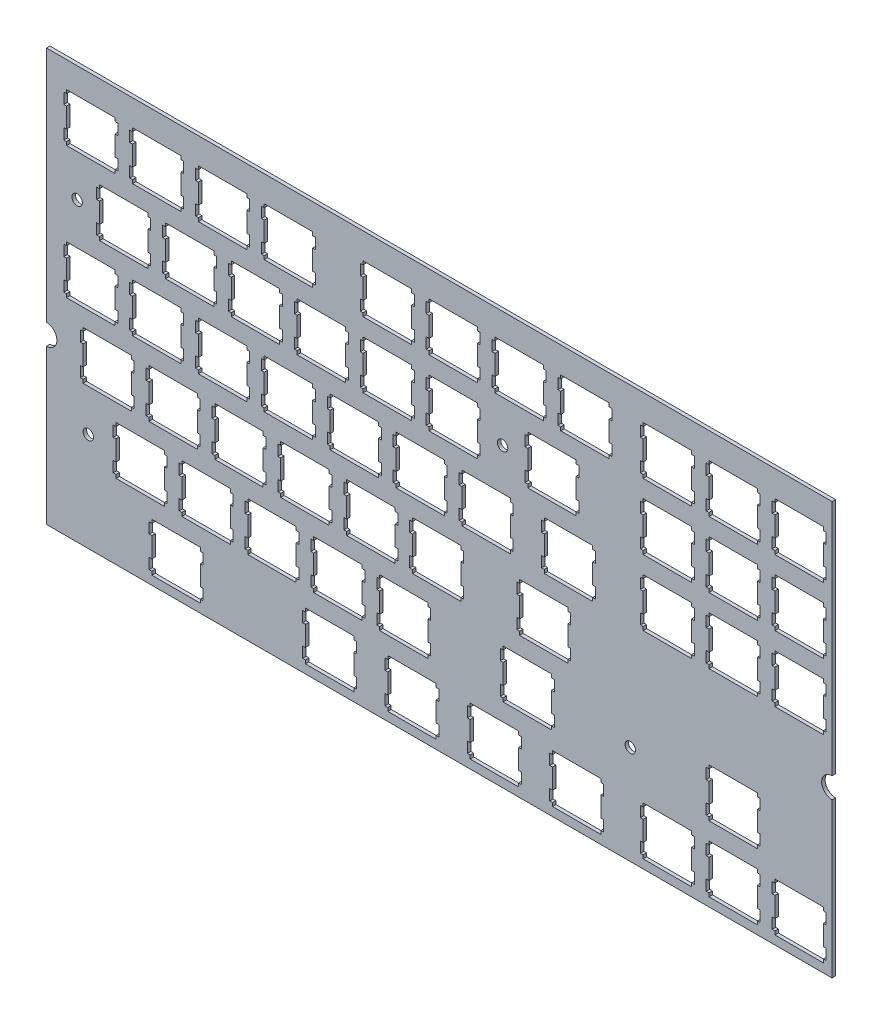
SolidWorks part; units mm, degrees
ref_plane "前视基准面" through (0, 0, 0) normal (0, 0, 1) x (1, 0, 0)
ref_plane "上视基准面" through (0, 0, 0) normal (0, 1, 0) x (1, 0, 0)
ref_plane "右视基准面" through (0, 0, 0) normal (1, 0, 0) x (0, 0, -1)
sketch "Model" plane through (0, 0, 0) normal (0, 0, 1) x (1, 0, 0)
  line L0 (406.675, 92.1112) -> (406.675, 91.1108)
  line L1 (406.675, 91.1108) -> (405.874, 91.1108)
  line L2 (405.874, 91.1108) -> (405.874, 88.0115)
  line L3 (405.874, 88.0115) -> (406.675, 88.0115)
  line L4 (406.675, 88.0115) -> (406.675, 82.21)
  line L5 (406.675, 82.21) -> (405.874, 82.21)
  line L6 (405.874, 82.21) -> (405.874, 79.1108)
  line L7 (405.874, 79.1108) -> (406.675, 79.1108)
  line L8 (406.675, 79.1108) -> (406.675, 78.1103)
  line L9 (406.675, 78.1103) -> (420.675, 78.1103)
  line L10 (420.675, 78.1103) -> (420.675, 79.1108)
  line L11 (420.675, 79.1108) -> (421.474, 79.1108)
  line L12 (421.474, 79.1108) -> (421.474, 82.21)
  line L13 (421.474, 82.21) -> (420.675, 82.21)
  line L14 (420.675, 82.21) -> (420.675, 88.0115)
  line L15 (420.675, 88.0115) -> (421.474, 88.0115)
  line L16 (421.474, 88.0115) -> (421.474, 91.1108)
  line L17 (421.474, 91.1108) -> (420.675, 91.1108)
  line L18 (420.675, 91.1108) -> (420.675, 92.1112)
  line L19 (420.675, 92.1112) -> (406.675, 92.1112)
  line L20 (387.625, 92.1112) -> (387.625, 91.1108)
  line L21 (387.625, 91.1108) -> (386.824, 91.1108)
  line L22 (386.824, 91.1108) -> (386.824, 88.0115)
  line L23 (386.824, 88.0115) -> (387.625, 88.0115)
  line L24 (387.625, 88.0115) -> (387.625, 82.21)
  line L25 (387.625, 82.21) -> (386.824, 82.21)
  line L26 (386.824, 82.21) -> (386.824, 79.1108)
  line L27 (386.824, 79.1108) -> (387.625, 79.1108)
  line L28 (387.625, 79.1108) -> (387.625, 78.1103)
  line L29 (387.625, 78.1103) -> (401.625, 78.1103)
  line L30 (401.625, 78.1103) -> (401.625, 79.1108)
  line L31 (401.625, 79.1108) -> (402.424, 79.1108)
  line L32 (402.424, 79.1108) -> (402.424, 82.21)
  line L33 (402.424, 82.21) -> (401.625, 82.21)
  line L34 (401.625, 82.21) -> (401.625, 88.0115)
  line L35 (401.625, 88.0115) -> (402.424, 88.0115)
  line L36 (402.424, 88.0115) -> (402.424, 91.1108)
  line L37 (402.424, 91.1108) -> (401.625, 91.1108)
  line L38 (401.625, 91.1108) -> (401.625, 92.1112)
  line L39 (401.625, 92.1112) -> (387.625, 92.1112)
  line L40 (368.575, 92.1112) -> (368.575, 91.1108)
  line L41 (368.575, 91.1108) -> (367.774, 91.1108)
  line L42 (367.774, 91.1108) -> (367.774, 88.0115)
  line L43 (367.774, 88.0115) -> (368.575, 88.0115)
  line L44 (368.575, 88.0115) -> (368.575, 82.21)
  line L45 (368.575, 82.21) -> (367.774, 82.21)
  line L46 (367.774, 82.21) -> (367.774, 79.1108)
  line L47 (367.774, 79.1108) -> (368.575, 79.1108)
  line L48 (368.575, 79.1108) -> (368.575, 78.1103)
  line L49 (368.575, 78.1103) -> (382.575, 78.1103)
  line L50 (382.575, 78.1103) -> (382.575, 79.1108)
  line L51 (382.575, 79.1108) -> (383.374, 79.1108)
  line L52 (383.374, 79.1108) -> (383.374, 82.21)
  line L53 (383.374, 82.21) -> (382.575, 82.21)
  line L54 (382.575, 82.21) -> (382.575, 88.0115)
  line L55 (382.575, 88.0115) -> (383.374, 88.0115)
  line L56 (383.374, 88.0115) -> (383.374, 91.1108)
  line L57 (383.374, 91.1108) -> (382.575, 91.1108)
  line L58 (382.575, 91.1108) -> (382.575, 92.1112)
  line L59 (382.575, 92.1112) -> (368.575, 92.1112)
  line L60 (342.38, 92.1112) -> (342.38, 91.1108)
  line L61 (342.38, 91.1108) -> (341.581, 91.1108)
  line L62 (341.581, 91.1108) -> (341.581, 88.0115)
  line L63 (341.581, 88.0115) -> (342.38, 88.0115)
  line L64 (342.38, 88.0115) -> (342.38, 82.21)
  line L65 (342.38, 82.21) -> (341.581, 82.21)
  line L66 (341.581, 82.21) -> (341.581, 79.1108)
  line L67 (341.581, 79.1108) -> (342.38, 79.1108)
  line L68 (342.38, 79.1108) -> (342.38, 78.1103)
  line L69 (342.38, 78.1103) -> (356.381, 78.1103)
  line L70 (356.381, 78.1103) -> (356.381, 79.1108)
  line L71 (356.381, 79.1108) -> (357.18, 79.1108)
  line L72 (357.18, 79.1108) -> (357.18, 82.21)
  line L73 (357.18, 82.21) -> (356.381, 82.21)
  line L74 (356.381, 82.21) -> (356.381, 88.0115)
  line L75 (356.381, 88.0115) -> (357.18, 88.0115)
  line L76 (357.18, 88.0115) -> (357.18, 91.1108)
  line L77 (357.18, 91.1108) -> (356.381, 91.1108)
  line L78 (356.381, 91.1108) -> (356.381, 92.1112)
  line L79 (356.381, 92.1112) -> (342.38, 92.1112)
  line L80 (318.569, 92.1112) -> (318.569, 91.1108)
  line L81 (318.569, 91.1108) -> (317.768, 91.1108)
  line L82 (317.768, 91.1108) -> (317.768, 88.0115)
  line L83 (317.768, 88.0115) -> (318.569, 88.0115)
  line L84 (318.569, 88.0115) -> (318.569, 82.21)
  line L85 (318.569, 82.21) -> (317.768, 82.21)
  line L86 (317.768, 82.21) -> (317.768, 79.1108)
  line L87 (317.768, 79.1108) -> (318.569, 79.1108)
  line L88 (318.569, 79.1108) -> (318.569, 78.1103)
  line L89 (318.569, 78.1103) -> (332.568, 78.1103)
  line L90 (332.568, 78.1103) -> (332.568, 79.1108)
  line L91 (332.568, 79.1108) -> (333.369, 79.1108)
  line L92 (333.369, 79.1108) -> (333.369, 82.21)
  line L93 (333.369, 82.21) -> (332.568, 82.21)
  line L94 (332.568, 82.21) -> (332.568, 88.0115)
  line L95 (332.568, 88.0115) -> (333.369, 88.0115)
  line L96 (333.369, 88.0115) -> (333.369, 91.1108)
  line L97 (333.369, 91.1108) -> (332.568, 91.1108)
  line L98 (332.568, 91.1108) -> (332.568, 92.1112)
  line L99 (332.568, 92.1112) -> (318.569, 92.1112)
  line L100 (294.755, 92.1112) -> (294.755, 91.1108)
  line L101 (294.755, 91.1108) -> (293.956, 91.1108)
  line L102 (293.956, 91.1108) -> (293.956, 88.0115)
  line L103 (293.956, 88.0115) -> (294.755, 88.0115)
  line L104 (294.755, 88.0115) -> (294.755, 82.21)
  line L105 (294.755, 82.21) -> (293.956, 82.21)
  line L106 (293.956, 82.21) -> (293.956, 79.1108)
  line L107 (293.956, 79.1108) -> (294.755, 79.1108)
  line L108 (294.755, 79.1108) -> (294.755, 78.1103)
  line L109 (294.755, 78.1103) -> (308.756, 78.1103)
  line L110 (308.756, 78.1103) -> (308.756, 79.1108)
  line L111 (308.756, 79.1108) -> (309.555, 79.1108)
  line L112 (309.555, 79.1108) -> (309.555, 82.21)
  line L113 (309.555, 82.21) -> (308.756, 82.21)
  line L114 (308.756, 82.21) -> (308.756, 88.0115)
  line L115 (308.756, 88.0115) -> (309.555, 88.0115)
  line L116 (309.555, 88.0115) -> (309.555, 91.1108)
  line L117 (309.555, 91.1108) -> (308.756, 91.1108)
  line L118 (308.756, 91.1108) -> (308.756, 92.1112)
  line L119 (308.756, 92.1112) -> (294.755, 92.1112)
  line L120 (270.944, 92.1112) -> (270.944, 91.1108)
  line L121 (270.944, 91.1108) -> (270.143, 91.1108)
  line L122 (270.143, 91.1108) -> (270.143, 88.0115)
  line L123 (270.143, 88.0115) -> (270.944, 88.0115)
  line L124 (270.944, 88.0115) -> (270.944, 82.21)
  line L125 (270.944, 82.21) -> (270.143, 82.21)
  line L126 (270.143, 82.21) -> (270.143, 79.1108)
  line L127 (270.143, 79.1108) -> (270.944, 79.1108)
  line L128 (270.944, 79.1108) -> (270.944, 78.1103)
  line L129 (270.944, 78.1103) -> (284.943, 78.1103)
  line L130 (284.943, 78.1103) -> (284.943, 79.1108)
  line L131 (284.943, 79.1108) -> (285.744, 79.1108)
  line L132 (285.744, 79.1108) -> (285.744, 82.21)
  line L133 (285.744, 82.21) -> (284.943, 82.21)
  line L134 (284.943, 82.21) -> (284.943, 88.0115)
  line L135 (284.943, 88.0115) -> (285.744, 88.0115)
  line L136 (285.744, 88.0115) -> (285.744, 91.1108)
  line L137 (285.744, 91.1108) -> (284.943, 91.1108)
  line L138 (284.943, 91.1108) -> (284.943, 92.1112)
  line L139 (284.943, 92.1112) -> (270.944, 92.1112)
  line L140 (387.625, 111.1597) -> (387.625, 110.1594)
  line L141 (387.625, 110.1594) -> (386.824, 110.1594)
  line L142 (386.824, 110.1594) -> (386.824, 107.0615)
  line L143 (386.824, 107.0615) -> (387.625, 107.0615)
  line L144 (387.625, 107.0615) -> (387.625, 101.26)
  line L145 (387.625, 101.26) -> (386.824, 101.26)
  line L146 (386.824, 101.26) -> (386.824, 98.1594)
  line L147 (386.824, 98.1594) -> (387.625, 98.1594)
  line L148 (387.625, 98.1594) -> (387.625, 97.1603)
  line L149 (387.625, 97.1603) -> (401.625, 97.1603)
  line L150 (401.625, 97.1603) -> (401.625, 98.1594)
  line L151 (401.625, 98.1594) -> (402.424, 98.1594)
  line L152 (402.424, 98.1594) -> (402.424, 101.26)
  line L153 (402.424, 101.26) -> (401.625, 101.26)
  line L154 (401.625, 101.26) -> (401.625, 107.0615)
  line L155 (401.625, 107.0615) -> (402.424, 107.0615)
  line L156 (402.424, 107.0615) -> (402.424, 110.1594)
  line L157 (402.424, 110.1594) -> (401.625, 110.1594)
  line L158 (401.625, 110.1594) -> (401.625, 111.1597)
  line L159 (401.625, 111.1597) -> (387.625, 111.1597)
  line L160 (292.375, 111.1597) -> (292.375, 110.1594)
  line L161 (292.375, 110.1594) -> (291.574, 110.1594)
  line L162 (291.574, 110.1594) -> (291.574, 107.0615)
  line L163 (291.574, 107.0615) -> (292.375, 107.0615)
  line L164 (292.375, 107.0615) -> (292.375, 101.26)
  line L165 (292.375, 101.26) -> (291.574, 101.26)
  line L166 (291.574, 101.26) -> (291.574, 98.1594)
  line L167 (291.574, 98.1594) -> (292.375, 98.1594)
  line L168 (292.375, 98.1594) -> (292.375, 97.1603)
  line L169 (292.375, 97.1603) -> (306.375, 97.1603)
  line L170 (306.375, 97.1603) -> (306.375, 98.1594)
  line L171 (306.375, 98.1594) -> (307.174, 98.1594)
  line L172 (307.174, 98.1594) -> (307.174, 101.26)
  line L173 (307.174, 101.26) -> (306.375, 101.26)
  line L174 (306.375, 101.26) -> (306.375, 107.0615)
  line L175 (306.375, 107.0615) -> (307.174, 107.0615)
  line L176 (307.174, 107.0615) -> (307.174, 110.1594)
  line L177 (307.174, 110.1594) -> (306.375, 110.1594)
  line L178 (306.375, 110.1594) -> (306.375, 111.1597)
  line L179 (306.375, 111.1597) -> (292.375, 111.1597)
  line L180 (273.325, 111.1597) -> (273.325, 110.1594)
  line L181 (273.325, 110.1594) -> (272.524, 110.1594)
  line L182 (272.524, 110.1594) -> (272.524, 107.0615)
  line L183 (272.524, 107.0615) -> (273.325, 107.0615)
  line L184 (273.325, 107.0615) -> (273.325, 101.26)
  line L185 (273.325, 101.26) -> (272.524, 101.26)
  line L186 (272.524, 101.26) -> (272.524, 98.1594)
  line L187 (272.524, 98.1594) -> (273.325, 98.1594)
  line L188 (273.325, 98.1594) -> (273.325, 97.1603)
  line L189 (273.325, 97.1603) -> (287.325, 97.1603)
  line L190 (287.325, 97.1603) -> (287.325, 98.1594)
  line L191 (287.325, 98.1594) -> (288.124, 98.1594)
  line L192 (288.124, 98.1594) -> (288.124, 101.26)
  line L193 (288.124, 101.26) -> (287.325, 101.26)
  line L194 (287.325, 101.26) -> (287.325, 107.0615)
  line L195 (287.325, 107.0615) -> (288.124, 107.0615)
  line L196 (288.124, 107.0615) -> (288.124, 110.1594)
  line L197 (288.124, 110.1594) -> (287.325, 110.1594)
  line L198 (287.325, 110.1594) -> (287.325, 111.1597)
  line L199 (287.325, 111.1597) -> (273.325, 111.1597)
  line L200 (254.275, 111.1597) -> (254.275, 110.1594)
  line L201 (254.275, 110.1594) -> (253.474, 110.1594)
  line L202 (253.474, 110.1594) -> (253.474, 107.0615)
  line L203 (253.474, 107.0615) -> (254.275, 107.0615)
  line L204 (254.275, 107.0615) -> (254.275, 101.26)
  line L205 (254.275, 101.26) -> (253.474, 101.26)
  line L206 (253.474, 101.26) -> (253.474, 98.1594)
  line L207 (253.474, 98.1594) -> (254.275, 98.1594)
  line L208 (254.275, 98.1594) -> (254.275, 97.1603)
  line L209 (254.275, 97.1603) -> (268.275, 97.1603)
  line L210 (268.275, 97.1603) -> (268.275, 98.1594)
  line L211 (268.275, 98.1594) -> (269.074, 98.1594)
  line L212 (269.074, 98.1594) -> (269.074, 101.26)
  line L213 (269.074, 101.26) -> (268.275, 101.26)
  line L214 (268.275, 101.26) -> (268.275, 107.0615)
  line L215 (268.275, 107.0615) -> (269.074, 107.0615)
  line L216 (269.074, 107.0615) -> (269.074, 110.1594)
  line L217 (269.074, 110.1594) -> (268.275, 110.1594)
  line L218 (268.275, 110.1594) -> (268.275, 111.1597)
  line L219 (268.275, 111.1597) -> (254.275, 111.1597)
  line L220 (235.225, 111.1597) -> (235.225, 110.1594)
  line L221 (235.225, 110.1594) -> (234.424, 110.1594)
  line L222 (234.424, 110.1594) -> (234.424, 107.0615)
  line L223 (234.424, 107.0615) -> (235.225, 107.0615)
  line L224 (235.225, 107.0615) -> (235.225, 101.26)
  line L225 (235.225, 101.26) -> (234.424, 101.26)
  line L226 (234.424, 101.26) -> (234.424, 98.1594)
  line L227 (234.424, 98.1594) -> (235.225, 98.1594)
  line L228 (235.225, 98.1594) -> (235.225, 97.1603)
  line L229 (235.225, 97.1603) -> (249.225, 97.1603)
  line L230 (249.225, 97.1603) -> (249.225, 98.1594)
  line L231 (249.225, 98.1594) -> (250.024, 98.1594)
  line L232 (250.024, 98.1594) -> (250.024, 101.26)
  line L233 (250.024, 101.26) -> (249.225, 101.26)
  line L234 (249.225, 101.26) -> (249.225, 107.0615)
  line L235 (249.225, 107.0615) -> (250.024, 107.0615)
  line L236 (250.024, 107.0615) -> (250.024, 110.1594)
  line L237 (250.024, 110.1594) -> (249.225, 110.1594)
  line L238 (249.225, 110.1594) -> (249.225, 111.1597)
  line L239 (249.225, 111.1597) -> (235.225, 111.1597)
  line L240 (216.175, 111.1597) -> (216.175, 110.1594)
  line L241 (216.175, 110.1594) -> (215.374, 110.1594)
  line L242 (215.374, 110.1594) -> (215.374, 107.0615)
  line L243 (215.374, 107.0615) -> (216.175, 107.0615)
  line L244 (216.175, 107.0615) -> (216.175, 101.26)
  line L245 (216.175, 101.26) -> (215.374, 101.26)
  line L246 (215.374, 101.26) -> (215.374, 98.1594)
  line L247 (215.374, 98.1594) -> (216.175, 98.1594)
  line L248 (216.175, 98.1594) -> (216.175, 97.1603)
  line L249 (216.175, 97.1603) -> (230.175, 97.1603)
  line L250 (230.175, 97.1603) -> (230.175, 98.1594)
  line L251 (230.175, 98.1594) -> (230.974, 98.1594)
  line L252 (230.974, 98.1594) -> (230.974, 101.26)
  line L253 (230.974, 101.26) -> (230.175, 101.26)
  line L254 (230.175, 101.26) -> (230.175, 107.0615)
  line L255 (230.175, 107.0615) -> (230.974, 107.0615)
  line L256 (230.974, 107.0615) -> (230.974, 110.1594)
  line L257 (230.974, 110.1594) -> (230.175, 110.1594)
  line L258 (230.175, 110.1594) -> (230.175, 111.1597)
  line L259 (230.175, 111.1597) -> (216.175, 111.1597)
  line L260 (332.855, 130.2098) -> (332.855, 129.2093)
  line L261 (332.855, 129.2093) -> (332.054, 129.2093)
  line L262 (332.054, 129.2093) -> (332.054, 126.1115)
  line L263 (332.054, 126.1115) -> (332.855, 126.1115)
  line L264 (332.855, 126.1115) -> (332.855, 120.3101)
  line L265 (332.855, 120.3101) -> (332.054, 120.3101)
  line L266 (332.054, 120.3101) -> (332.054, 117.2095)
  line L267 (332.054, 117.2095) -> (332.855, 117.2095)
  line L268 (332.855, 117.2095) -> (332.855, 116.2105)
  line L269 (332.855, 116.2105) -> (346.856, 116.2105)
  line L270 (346.856, 116.2105) -> (346.856, 117.2095)
  line L271 (346.856, 117.2095) -> (347.655, 117.2095)
  line L272 (347.655, 117.2095) -> (347.655, 120.3101)
  line L273 (347.655, 120.3101) -> (346.856, 120.3101)
  line L274 (346.856, 120.3101) -> (346.856, 126.1115)
  line L275 (346.856, 126.1115) -> (347.655, 126.1115)
  line L276 (347.655, 126.1115) -> (347.655, 129.2093)
  line L277 (347.655, 129.2093) -> (346.856, 129.2093)
  line L278 (346.856, 129.2093) -> (346.856, 130.2098)
  line L279 (346.856, 130.2098) -> (332.855, 130.2098)
  line L280 (301.9, 130.2098) -> (301.9, 129.2093)
  line L281 (301.9, 129.2093) -> (301.099, 129.2093)
  line L282 (301.099, 129.2093) -> (301.099, 126.1115)
  line L283 (301.099, 126.1115) -> (301.9, 126.1115)
  line L284 (301.9, 126.1115) -> (301.9, 120.3101)
  line L285 (301.9, 120.3101) -> (301.099, 120.3101)
  line L286 (301.099, 120.3101) -> (301.099, 117.2095)
  line L287 (301.099, 117.2095) -> (301.9, 117.2095)
  line L288 (301.9, 117.2095) -> (301.9, 116.2105)
  line L289 (301.9, 116.2105) -> (315.9, 116.2105)
  line L290 (315.9, 116.2105) -> (315.9, 117.2095)
  line L291 (315.9, 117.2095) -> (316.699, 117.2095)
  line L292 (316.699, 117.2095) -> (316.699, 120.3101)
  line L293 (316.699, 120.3101) -> (315.9, 120.3101)
  line L294 (315.9, 120.3101) -> (315.9, 126.1115)
  line L295 (315.9, 126.1115) -> (316.699, 126.1115)
  line L296 (316.699, 126.1115) -> (316.699, 129.2093)
  line L297 (316.699, 129.2093) -> (315.9, 129.2093)
  line L298 (315.9, 129.2093) -> (315.9, 130.2098)
  line L299 (315.9, 130.2098) -> (301.9, 130.2098)
  line L300 (282.85, 130.2098) -> (282.85, 129.2093)
  line L301 (282.85, 129.2093) -> (282.049, 129.2093)
  line L302 (282.049, 129.2093) -> (282.049, 126.1115)
  line L303 (282.049, 126.1115) -> (282.85, 126.1115)
  line L304 (282.85, 126.1115) -> (282.85, 120.3101)
  line L305 (282.85, 120.3101) -> (282.049, 120.3101)
  line L306 (282.049, 120.3101) -> (282.049, 117.2095)
  line L307 (282.049, 117.2095) -> (282.85, 117.2095)
  line L308 (282.85, 117.2095) -> (282.85, 116.2105)
  line L309 (282.85, 116.2105) -> (296.85, 116.2105)
  line L310 (296.85, 116.2105) -> (296.85, 117.2095)
  line L311 (296.85, 117.2095) -> (297.649, 117.2095)
  line L312 (297.649, 117.2095) -> (297.649, 120.3101)
  line L313 (297.649, 120.3101) -> (296.85, 120.3101)
  line L314 (296.85, 120.3101) -> (296.85, 126.1115)
  line L315 (296.85, 126.1115) -> (297.649, 126.1115)
  line L316 (297.649, 126.1115) -> (297.649, 129.2093)
  line L317 (297.649, 129.2093) -> (296.85, 129.2093)
  line L318 (296.85, 129.2093) -> (296.85, 130.2098)
  line L319 (296.85, 130.2098) -> (282.85, 130.2098)
  line L320 (263.8, 130.2098) -> (263.8, 129.2093)
  line L321 (263.8, 129.2093) -> (262.999, 129.2093)
  line L322 (262.999, 129.2093) -> (262.999, 126.1115)
  line L323 (262.999, 126.1115) -> (263.8, 126.1115)
  line L324 (263.8, 126.1115) -> (263.8, 120.3101)
  line L325 (263.8, 120.3101) -> (262.999, 120.3101)
  line L326 (262.999, 120.3101) -> (262.999, 117.2095)
  line L327 (262.999, 117.2095) -> (263.8, 117.2095)
  line L328 (263.8, 117.2095) -> (263.8, 116.2105)
  line L329 (263.8, 116.2105) -> (277.8, 116.2105)
  line L330 (277.8, 116.2105) -> (277.8, 117.2095)
  line L331 (277.8, 117.2095) -> (278.599, 117.2095)
  line L332 (278.599, 117.2095) -> (278.599, 120.3101)
  line L333 (278.599, 120.3101) -> (277.8, 120.3101)
  line L334 (277.8, 120.3101) -> (277.8, 126.1115)
  line L335 (277.8, 126.1115) -> (278.599, 126.1115)
  line L336 (278.599, 126.1115) -> (278.599, 129.2093)
  line L337 (278.599, 129.2093) -> (277.8, 129.2093)
  line L338 (277.8, 129.2093) -> (277.8, 130.2098)
  line L339 (277.8, 130.2098) -> (263.8, 130.2098)
  line L340 (244.75, 130.2098) -> (244.75, 129.2093)
  line L341 (244.75, 129.2093) -> (243.949, 129.2093)
  line L342 (243.949, 129.2093) -> (243.949, 126.1115)
  line L343 (243.949, 126.1115) -> (244.75, 126.1115)
  line L344 (244.75, 126.1115) -> (244.75, 120.3101)
  line L345 (244.75, 120.3101) -> (243.949, 120.3101)
  line L346 (243.949, 120.3101) -> (243.949, 117.2095)
  line L347 (243.949, 117.2095) -> (244.75, 117.2095)
  line L348 (244.75, 117.2095) -> (244.75, 116.2105)
  line L349 (244.75, 116.2105) -> (258.75, 116.2105)
  line L350 (258.75, 116.2105) -> (258.75, 117.2095)
  line L351 (258.75, 117.2095) -> (259.549, 117.2095)
  line L352 (259.549, 117.2095) -> (259.549, 120.3101)
  line L353 (259.549, 120.3101) -> (258.75, 120.3101)
  line L354 (258.75, 120.3101) -> (258.75, 126.1115)
  line L355 (258.75, 126.1115) -> (259.549, 126.1115)
  line L356 (259.549, 126.1115) -> (259.549, 129.2093)
  line L357 (259.549, 129.2093) -> (258.75, 129.2093)
  line L358 (258.75, 129.2093) -> (258.75, 130.2098)
  line L359 (258.75, 130.2098) -> (244.75, 130.2098)
  line L360 (225.7, 130.2098) -> (225.7, 129.2093)
  line L361 (225.7, 129.2093) -> (224.899, 129.2093)
  line L362 (224.899, 129.2093) -> (224.899, 126.1115)
  line L363 (224.899, 126.1115) -> (225.7, 126.1115)
  line L364 (225.7, 126.1115) -> (225.7, 120.3101)
  line L365 (225.7, 120.3101) -> (224.899, 120.3101)
  line L366 (224.899, 120.3101) -> (224.899, 117.2095)
  line L367 (224.899, 117.2095) -> (225.7, 117.2095)
  line L368 (225.7, 117.2095) -> (225.7, 116.2105)
  line L369 (225.7, 116.2105) -> (239.7, 116.2105)
  line L370 (239.7, 116.2105) -> (239.7, 117.2095)
  line L371 (239.7, 117.2095) -> (240.499, 117.2095)
  line L372 (240.499, 117.2095) -> (240.499, 120.3101)
  line L373 (240.499, 120.3101) -> (239.7, 120.3101)
  line L374 (239.7, 120.3101) -> (239.7, 126.1115)
  line L375 (239.7, 126.1115) -> (240.499, 126.1115)
  line L376 (240.499, 126.1115) -> (240.499, 129.2093)
  line L377 (240.499, 129.2093) -> (239.7, 129.2093)
  line L378 (239.7, 129.2093) -> (239.7, 130.2098)
  line L379 (239.7, 130.2098) -> (225.7, 130.2098)
  line L380 (206.65, 130.2098) -> (206.65, 129.2093)
  line L381 (206.65, 129.2093) -> (205.849, 129.2093)
  line L382 (205.849, 129.2093) -> (205.849, 126.1115)
  line L383 (205.849, 126.1115) -> (206.65, 126.1115)
  line L384 (206.65, 126.1115) -> (206.65, 120.3101)
  line L385 (206.65, 120.3101) -> (205.849, 120.3101)
  line L386 (205.849, 120.3101) -> (205.849, 117.2095)
  line L387 (205.849, 117.2095) -> (206.65, 117.2095)
  line L388 (206.65, 117.2095) -> (206.65, 116.2105)
  line L389 (206.65, 116.2105) -> (220.65, 116.2105)
  line L390 (220.65, 116.2105) -> (220.65, 117.2095)
  line L391 (220.65, 117.2095) -> (221.449, 117.2095)
  line L392 (221.449, 117.2095) -> (221.449, 120.3101)
  line L393 (221.449, 120.3101) -> (220.65, 120.3101)
  line L394 (220.65, 120.3101) -> (220.65, 126.1115)
  line L395 (220.65, 126.1115) -> (221.449, 126.1115)
  line L396 (221.449, 126.1115) -> (221.449, 129.2093)
  line L397 (221.449, 129.2093) -> (220.65, 129.2093)
  line L398 (220.65, 129.2093) -> (220.65, 130.2098)
  line L399 (220.65, 130.2098) -> (206.65, 130.2098)
  line L400 (406.675, 149.2598) -> (406.675, 148.2593)
  line L401 (406.675, 148.2593) -> (405.874, 148.2593)
  line L402 (405.874, 148.2593) -> (405.874, 145.1601)
  line L403 (405.874, 145.1601) -> (406.675, 145.1601)
  line L404 (406.675, 145.1601) -> (406.675, 139.3601)
  line L405 (406.675, 139.3601) -> (405.874, 139.3601)
  line L406 (405.874, 139.3601) -> (405.874, 136.2595)
  line L407 (405.874, 136.2595) -> (406.675, 136.2595)
  line L408 (406.675, 136.2595) -> (406.675, 135.2605)
  line L409 (406.675, 135.2605) -> (420.675, 135.2605)
  line L410 (420.675, 135.2605) -> (420.675, 136.2595)
  line L411 (420.675, 136.2595) -> (421.474, 136.2595)
  line L412 (421.474, 136.2595) -> (421.474, 139.3601)
  line L413 (421.474, 139.3601) -> (420.675, 139.3601)
  line L414 (420.675, 139.3601) -> (420.675, 145.1601)
  line L415 (420.675, 145.1601) -> (421.474, 145.1601)
  line L416 (421.474, 145.1601) -> (421.474, 148.2593)
  line L417 (421.474, 148.2593) -> (420.675, 148.2593)
  line L418 (420.675, 148.2593) -> (420.675, 149.2598)
  line L419 (420.675, 149.2598) -> (406.675, 149.2598)
  line L420 (387.625, 149.2598) -> (387.625, 148.2593)
  line L421 (387.625, 148.2593) -> (386.824, 148.2593)
  line L422 (386.824, 148.2593) -> (386.824, 145.1601)
  line L423 (386.824, 145.1601) -> (387.625, 145.1601)
  line L424 (387.625, 145.1601) -> (387.625, 139.3601)
  line L425 (387.625, 139.3601) -> (386.824, 139.3601)
  line L426 (386.824, 139.3601) -> (386.824, 136.2595)
  line L427 (386.824, 136.2595) -> (387.625, 136.2595)
  line L428 (387.625, 136.2595) -> (387.625, 135.2605)
  line L429 (387.625, 135.2605) -> (401.625, 135.2605)
  line L430 (401.625, 135.2605) -> (401.625, 136.2595)
  line L431 (401.625, 136.2595) -> (402.424, 136.2595)
  line L432 (402.424, 136.2595) -> (402.424, 139.3601)
  line L433 (402.424, 139.3601) -> (401.625, 139.3601)
  line L434 (401.625, 139.3601) -> (401.625, 145.1601)
  line L435 (401.625, 145.1601) -> (402.424, 145.1601)
  line L436 (402.424, 145.1601) -> (402.424, 148.2593)
  line L437 (402.424, 148.2593) -> (401.625, 148.2593)
  line L438 (401.625, 148.2593) -> (401.625, 149.2598)
  line L439 (401.625, 149.2598) -> (387.625, 149.2598)
  line L440 (368.575, 149.2598) -> (368.575, 148.2593)
  line L441 (368.575, 148.2593) -> (367.774, 148.2593)
  line L442 (367.774, 148.2593) -> (367.774, 145.1601)
  line L443 (367.774, 145.1601) -> (368.575, 145.1601)
  line L444 (368.575, 145.1601) -> (368.575, 139.3601)
  line L445 (368.575, 139.3601) -> (367.774, 139.3601)
  line L446 (367.774, 139.3601) -> (367.774, 136.2595)
  line L447 (367.774, 136.2595) -> (368.575, 136.2595)
  line L448 (368.575, 136.2595) -> (368.575, 135.2605)
  line L449 (368.575, 135.2605) -> (382.575, 135.2605)
  line L450 (382.575, 135.2605) -> (382.575, 136.2595)
  line L451 (382.575, 136.2595) -> (383.374, 136.2595)
  line L452 (383.374, 136.2595) -> (383.374, 139.3601)
  line L453 (383.374, 139.3601) -> (382.575, 139.3601)
  line L454 (382.575, 139.3601) -> (382.575, 145.1601)
  line L455 (382.575, 145.1601) -> (383.374, 145.1601)
  line L456 (383.374, 145.1601) -> (383.374, 148.2593)
  line L457 (383.374, 148.2593) -> (382.575, 148.2593)
  line L458 (382.575, 148.2593) -> (382.575, 149.2598)
  line L459 (382.575, 149.2598) -> (368.575, 149.2598)
  line L460 (340, 149.2598) -> (340, 148.2593)
  line L461 (340, 148.2593) -> (339.199, 148.2593)
  line L462 (339.199, 148.2593) -> (339.199, 145.1601)
  line L463 (339.199, 145.1601) -> (340, 145.1601)
  line L464 (340, 145.1601) -> (340, 139.3601)
  line L465 (340, 139.3601) -> (339.199, 139.3601)
  line L466 (339.199, 139.3601) -> (339.199, 136.2595)
  line L467 (339.199, 136.2595) -> (340, 136.2595)
  line L468 (340, 136.2595) -> (340, 135.2605)
  line L469 (340, 135.2605) -> (354, 135.2605)
  line L470 (354, 135.2605) -> (354, 136.2595)
  line L471 (354, 136.2595) -> (354.799, 136.2595)
  line L472 (354.799, 136.2595) -> (354.799, 139.3601)
  line L473 (354.799, 139.3601) -> (354, 139.3601)
  line L474 (354, 139.3601) -> (354, 145.1601)
  line L475 (354, 145.1601) -> (354.799, 145.1601)
  line L476 (354.799, 145.1601) -> (354.799, 148.2593)
  line L477 (354.799, 148.2593) -> (354, 148.2593)
  line L478 (354, 148.2593) -> (354, 149.2598)
  line L479 (354, 149.2598) -> (340, 149.2598)
  line L480 (316.188, 149.2598) -> (316.188, 148.2593)
  line L481 (316.188, 148.2593) -> (315.387, 148.2593)
  line L482 (315.387, 148.2593) -> (315.387, 145.1601)
  line L483 (315.387, 145.1601) -> (316.188, 145.1601)
  line L484 (316.188, 145.1601) -> (316.188, 139.3601)
  line L485 (316.188, 139.3601) -> (315.387, 139.3601)
  line L486 (315.387, 139.3601) -> (315.387, 136.2595)
  line L487 (315.387, 136.2595) -> (316.188, 136.2595)
  line L488 (316.188, 136.2595) -> (316.188, 135.2605)
  line L489 (316.188, 135.2605) -> (330.187, 135.2605)
  line L490 (330.187, 135.2605) -> (330.187, 136.2595)
  line L491 (330.187, 136.2595) -> (330.988, 136.2595)
  line L492 (330.988, 136.2595) -> (330.988, 139.3601)
  line L493 (330.988, 139.3601) -> (330.187, 139.3601)
  line L494 (330.187, 139.3601) -> (330.187, 145.1601)
  line L495 (330.187, 145.1601) -> (330.988, 145.1601)
  line L496 (330.988, 145.1601) -> (330.988, 148.2593)
  line L497 (330.988, 148.2593) -> (330.187, 148.2593)
  line L498 (330.187, 148.2593) -> (330.187, 149.2598)
  line L499 (330.187, 149.2598) -> (316.188, 149.2598)
  line L500 (297.138, 149.2598) -> (297.138, 148.2593)
  line L501 (297.138, 148.2593) -> (296.337, 148.2593)
  line L502 (296.337, 148.2593) -> (296.337, 145.1601)
  line L503 (296.337, 145.1601) -> (297.138, 145.1601)
  line L504 (297.138, 145.1601) -> (297.138, 139.3601)
  line L505 (297.138, 139.3601) -> (296.337, 139.3601)
  line L506 (296.337, 139.3601) -> (296.337, 136.2595)
  line L507 (296.337, 136.2595) -> (297.138, 136.2595)
  line L508 (297.138, 136.2595) -> (297.138, 135.2605)
  line L509 (297.138, 135.2605) -> (311.137, 135.2605)
  line L510 (311.137, 135.2605) -> (311.137, 136.2595)
  line L511 (311.137, 136.2595) -> (311.938, 136.2595)
  line L512 (311.938, 136.2595) -> (311.938, 139.3601)
  line L513 (311.938, 139.3601) -> (311.137, 139.3601)
  line L514 (311.137, 139.3601) -> (311.137, 145.1601)
  line L515 (311.137, 145.1601) -> (311.938, 145.1601)
  line L516 (311.938, 145.1601) -> (311.938, 148.2593)
  line L517 (311.938, 148.2593) -> (311.137, 148.2593)
  line L518 (311.137, 148.2593) -> (311.137, 149.2598)
  line L519 (311.137, 149.2598) -> (297.138, 149.2598)
  line L520 (278.088, 149.2598) -> (278.088, 148.2593)
  line L521 (278.088, 148.2593) -> (277.287, 148.2593)
  line L522 (277.287, 148.2593) -> (277.287, 145.1601)
  line L523 (277.287, 145.1601) -> (278.088, 145.1601)
  line L524 (278.088, 145.1601) -> (278.088, 139.3601)
  line L525 (278.088, 139.3601) -> (277.287, 139.3601)
  line L526 (277.287, 139.3601) -> (277.287, 136.2595)
  line L527 (277.287, 136.2595) -> (278.088, 136.2595)
  line L528 (278.088, 136.2595) -> (278.088, 135.2605)
  line L529 (278.088, 135.2605) -> (292.087, 135.2605)
  line L530 (292.087, 135.2605) -> (292.087, 136.2595)
  line L531 (292.087, 136.2595) -> (292.888, 136.2595)
  line L532 (292.888, 136.2595) -> (292.888, 139.3601)
  line L533 (292.888, 139.3601) -> (292.087, 139.3601)
  line L534 (292.087, 139.3601) -> (292.087, 145.1601)
  line L535 (292.087, 145.1601) -> (292.888, 145.1601)
  line L536 (292.888, 145.1601) -> (292.888, 148.2593)
  line L537 (292.888, 148.2593) -> (292.087, 148.2593)
  line L538 (292.087, 148.2593) -> (292.087, 149.2598)
  line L539 (292.087, 149.2598) -> (278.088, 149.2598)
  line L540 (259.038, 149.2598) -> (259.038, 148.2593)
  line L541 (259.038, 148.2593) -> (258.237, 148.2593)
  line L542 (258.237, 148.2593) -> (258.237, 145.1601)
  line L543 (258.237, 145.1601) -> (259.038, 145.1601)
  line L544 (259.038, 145.1601) -> (259.038, 139.3601)
  line L545 (259.038, 139.3601) -> (258.237, 139.3601)
  line L546 (258.237, 139.3601) -> (258.237, 136.2595)
  line L547 (258.237, 136.2595) -> (259.038, 136.2595)
  line L548 (259.038, 136.2595) -> (259.038, 135.2605)
  line L549 (259.038, 135.2605) -> (273.037, 135.2605)
  line L550 (273.037, 135.2605) -> (273.037, 136.2595)
  line L551 (273.037, 136.2595) -> (273.838, 136.2595)
  line L552 (273.838, 136.2595) -> (273.838, 139.3601)
  line L553 (273.838, 139.3601) -> (273.037, 139.3601)
  line L554 (273.037, 139.3601) -> (273.037, 145.1601)
  line L555 (273.037, 145.1601) -> (273.838, 145.1601)
  line L556 (273.838, 145.1601) -> (273.838, 148.2593)
  line L557 (273.838, 148.2593) -> (273.037, 148.2593)
  line L558 (273.037, 148.2593) -> (273.037, 149.2598)
  line L559 (273.037, 149.2598) -> (259.038, 149.2598)
  line L560 (239.988, 149.2598) -> (239.988, 148.2593)
  line L561 (239.988, 148.2593) -> (239.187, 148.2593)
  line L562 (239.187, 148.2593) -> (239.187, 145.1601)
  line L563 (239.187, 145.1601) -> (239.988, 145.1601)
  line L564 (239.988, 145.1601) -> (239.988, 139.3601)
  line L565 (239.988, 139.3601) -> (239.187, 139.3601)
  line L566 (239.187, 139.3601) -> (239.187, 136.2595)
  line L567 (239.187, 136.2595) -> (239.988, 136.2595)
  line L568 (239.988, 136.2595) -> (239.988, 135.2605)
  line L569 (239.988, 135.2605) -> (253.987, 135.2605)
  line L570 (253.987, 135.2605) -> (253.987, 136.2595)
  line L571 (253.987, 136.2595) -> (254.788, 136.2595)
  line L572 (254.788, 136.2595) -> (254.788, 139.3601)
  line L573 (254.788, 139.3601) -> (253.987, 139.3601)
  line L574 (253.987, 139.3601) -> (253.987, 145.1601)
  line L575 (253.987, 145.1601) -> (254.788, 145.1601)
  line L576 (254.788, 145.1601) -> (254.788, 148.2593)
  line L577 (254.788, 148.2593) -> (253.987, 148.2593)
  line L578 (253.987, 148.2593) -> (253.987, 149.2598)
  line L579 (253.987, 149.2598) -> (239.988, 149.2598)
  line L580 (220.938, 149.2598) -> (220.938, 148.2593)
  line L581 (220.938, 148.2593) -> (220.137, 148.2593)
  line L582 (220.137, 148.2593) -> (220.137, 145.1601)
  line L583 (220.137, 145.1601) -> (220.938, 145.1601)
  line L584 (220.938, 145.1601) -> (220.938, 139.3601)
  line L585 (220.938, 139.3601) -> (220.137, 139.3601)
  line L586 (220.137, 139.3601) -> (220.137, 136.2595)
  line L587 (220.137, 136.2595) -> (220.938, 136.2595)
  line L588 (220.938, 136.2595) -> (220.938, 135.2605)
  line L589 (220.938, 135.2605) -> (234.937, 135.2605)
  line L590 (234.937, 135.2605) -> (234.937, 136.2595)
  line L591 (234.937, 136.2595) -> (235.738, 136.2595)
  line L592 (235.738, 136.2595) -> (235.738, 139.3601)
  line L593 (235.738, 139.3601) -> (234.937, 139.3601)
  line L594 (234.937, 139.3601) -> (234.937, 145.1601)
  line L595 (234.937, 145.1601) -> (235.738, 145.1601)
  line L596 (235.738, 145.1601) -> (235.738, 148.2593)
  line L597 (235.738, 148.2593) -> (234.937, 148.2593)
  line L598 (234.937, 148.2593) -> (234.937, 149.2598)
  line L599 (234.937, 149.2598) -> (220.938, 149.2598)
  line L600 (201.888, 135.2605) -> (215.887, 135.2605)
  line L601 (215.887, 135.2605) -> (215.887, 136.2595)
  line L602 (215.887, 136.2595) -> (216.688, 136.2595)
  line L603 (216.688, 136.2595) -> (216.688, 139.3601)
  line L604 (216.688, 139.3601) -> (215.887, 139.3601)
  line L605 (215.887, 139.3601) -> (215.887, 145.1601)
  line L606 (215.887, 145.1601) -> (216.688, 145.1601)
  line L607 (216.688, 145.1601) -> (216.688, 148.2593)
  line L608 (216.688, 148.2593) -> (215.887, 148.2593)
  line L609 (215.887, 148.2593) -> (215.887, 149.2598)
  line L610 (215.887, 149.2598) -> (201.888, 149.2598)
  line L611 (406.675, 168.3098) -> (406.675, 167.3093)
  line L612 (406.675, 167.3093) -> (405.874, 167.3093)
  line L613 (405.874, 167.3093) -> (405.874, 164.2101)
  line L614 (405.874, 164.2101) -> (406.675, 164.2101)
  line L615 (406.675, 164.2101) -> (406.675, 158.4101)
  line L616 (406.675, 158.4101) -> (405.874, 158.4101)
  line L617 (405.874, 158.4101) -> (405.874, 155.3095)
  line L618 (405.874, 155.3095) -> (406.675, 155.3095)
  line L619 (406.675, 155.3095) -> (406.675, 154.3105)
  line L620 (406.675, 154.3105) -> (420.675, 154.3105)
  line L621 (420.675, 154.3105) -> (420.675, 155.3095)
  line L622 (420.675, 155.3095) -> (421.474, 155.3095)
  line L623 (421.474, 155.3095) -> (421.474, 158.4101)
  line L624 (421.474, 158.4101) -> (420.675, 158.4101)
  line L625 (420.675, 158.4101) -> (420.675, 164.2101)
  line L626 (420.675, 164.2101) -> (421.474, 164.2101)
  line L627 (421.474, 164.2101) -> (421.474, 167.3093)
  line L628 (421.474, 167.3093) -> (420.675, 167.3093)
  line L629 (420.675, 167.3093) -> (420.675, 168.3098)
  line L630 (420.675, 168.3098) -> (406.675, 168.3098)
  line L631 (387.625, 168.3098) -> (387.625, 167.3093)
  line L632 (387.625, 167.3093) -> (386.824, 167.3093)
  line L633 (386.824, 167.3093) -> (386.824, 164.2101)
  line L634 (386.824, 164.2101) -> (387.625, 164.2101)
  line L635 (387.625, 164.2101) -> (387.625, 158.4101)
  line L636 (387.625, 158.4101) -> (386.824, 158.4101)
  line L637 (386.824, 158.4101) -> (386.824, 155.3095)
  line L638 (386.824, 155.3095) -> (387.625, 155.3095)
  line L639 (387.625, 155.3095) -> (387.625, 154.3105)
  line L640 (387.625, 154.3105) -> (401.625, 154.3105)
  line L641 (401.625, 154.3105) -> (401.625, 155.3095)
  line L642 (401.625, 155.3095) -> (402.424, 155.3095)
  line L643 (402.424, 155.3095) -> (402.424, 158.4101)
  line L644 (402.424, 158.4101) -> (401.625, 158.4101)
  line L645 (401.625, 158.4101) -> (401.625, 164.2101)
  line L646 (401.625, 164.2101) -> (402.424, 164.2101)
  line L647 (402.424, 164.2101) -> (402.424, 167.3093)
  line L648 (402.424, 167.3093) -> (401.625, 167.3093)
  line L649 (401.625, 167.3093) -> (401.625, 168.3098)
  line L650 (401.625, 168.3098) -> (387.625, 168.3098)
  line L651 (368.575, 168.3098) -> (368.575, 167.3093)
  line L652 (368.575, 167.3093) -> (367.774, 167.3093)
  line L653 (367.774, 167.3093) -> (367.774, 164.2101)
  line L654 (367.774, 164.2101) -> (368.575, 164.2101)
  line L655 (368.575, 164.2101) -> (368.575, 158.4101)
  line L656 (368.575, 158.4101) -> (367.774, 158.4101)
  line L657 (367.774, 158.4101) -> (367.774, 155.3095)
  line L658 (367.774, 155.3095) -> (368.575, 155.3095)
  line L659 (368.575, 155.3095) -> (368.575, 154.3105)
  line L660 (368.575, 154.3105) -> (382.575, 154.3105)
  line L661 (382.575, 154.3105) -> (382.575, 155.3095)
  line L662 (382.575, 155.3095) -> (383.374, 155.3095)
  line L663 (383.374, 155.3095) -> (383.374, 158.4101)
  line L664 (383.374, 158.4101) -> (382.575, 158.4101)
  line L665 (382.575, 158.4101) -> (382.575, 164.2101)
  line L666 (382.575, 164.2101) -> (383.374, 164.2101)
  line L667 (383.374, 164.2101) -> (383.374, 167.3093)
  line L668 (383.374, 167.3093) -> (382.575, 167.3093)
  line L669 (382.575, 167.3093) -> (382.575, 168.3098)
  line L670 (382.575, 168.3098) -> (368.575, 168.3098)
  line L671 (306.663, 168.3098) -> (306.663, 167.3093)
  line L672 (306.663, 167.3093) -> (305.862, 167.3093)
  line L673 (305.862, 167.3093) -> (305.862, 164.2101)
  line L674 (305.862, 164.2101) -> (306.663, 164.2101)
  line L675 (306.663, 164.2101) -> (306.663, 158.4101)
  line L676 (306.663, 158.4101) -> (305.862, 158.4101)
  line L677 (305.862, 158.4101) -> (305.862, 155.3095)
  line L678 (305.862, 155.3095) -> (306.663, 155.3095)
  line L679 (306.663, 155.3095) -> (306.663, 154.3105)
  line L680 (306.663, 154.3105) -> (320.662, 154.3105)
  line L681 (320.662, 154.3105) -> (320.662, 155.3095)
  line L682 (320.662, 155.3095) -> (321.463, 155.3095)
  line L683 (321.463, 155.3095) -> (321.463, 158.4101)
  line L684 (321.463, 158.4101) -> (320.662, 158.4101)
  line L685 (320.662, 158.4101) -> (320.662, 164.2101)
  line L686 (320.662, 164.2101) -> (321.463, 164.2101)
  line L687 (321.463, 164.2101) -> (321.463, 167.3093)
  line L688 (321.463, 167.3093) -> (320.662, 167.3093)
  line L689 (320.662, 167.3093) -> (320.662, 168.3098)
  line L690 (320.662, 168.3098) -> (306.663, 168.3098)
  line L691 (287.613, 168.3098) -> (287.613, 167.3093)
  line L692 (287.613, 167.3093) -> (286.812, 167.3093)
  line L693 (286.812, 167.3093) -> (286.812, 164.2101)
  line L694 (286.812, 164.2101) -> (287.613, 164.2101)
  line L695 (287.613, 164.2101) -> (287.613, 158.4101)
  line L696 (287.613, 158.4101) -> (286.812, 158.4101)
  line L697 (286.812, 158.4101) -> (286.812, 155.3095)
  line L698 (286.812, 155.3095) -> (287.613, 155.3095)
  line L699 (287.613, 155.3095) -> (287.613, 154.3105)
  line L700 (287.613, 154.3105) -> (301.612, 154.3105)
  line L701 (301.612, 154.3105) -> (301.612, 155.3095)
  line L702 (301.612, 155.3095) -> (302.413, 155.3095)
  line L703 (302.413, 155.3095) -> (302.413, 158.4101)
  line L704 (302.413, 158.4101) -> (301.612, 158.4101)
  line L705 (301.612, 158.4101) -> (301.612, 164.2101)
  line L706 (301.612, 164.2101) -> (302.413, 164.2101)
  line L707 (302.413, 164.2101) -> (302.413, 167.3093)
  line L708 (302.413, 167.3093) -> (301.612, 167.3093)
  line L709 (301.612, 167.3093) -> (301.612, 168.3098)
  line L710 (301.612, 168.3098) -> (287.613, 168.3098)
  line L711 (268.563, 168.3098) -> (268.563, 167.3093)
  line L712 (268.563, 167.3093) -> (267.762, 167.3093)
  line L713 (267.762, 167.3093) -> (267.762, 164.2101)
  line L714 (267.762, 164.2101) -> (268.563, 164.2101)
  line L715 (268.563, 164.2101) -> (268.563, 158.4101)
  line L716 (268.563, 158.4101) -> (267.762, 158.4101)
  line L717 (267.762, 158.4101) -> (267.762, 155.3095)
  line L718 (267.762, 155.3095) -> (268.563, 155.3095)
  line L719 (268.563, 155.3095) -> (268.563, 154.3105)
  line L720 (268.563, 154.3105) -> (282.562, 154.3105)
  line L721 (282.562, 154.3105) -> (282.562, 155.3095)
  line L722 (282.562, 155.3095) -> (283.363, 155.3095)
  line L723 (283.363, 155.3095) -> (283.363, 158.4101)
  line L724 (283.363, 158.4101) -> (282.562, 158.4101)
  line L725 (282.562, 158.4101) -> (282.562, 164.2101)
  line L726 (282.562, 164.2101) -> (283.363, 164.2101)
  line L727 (283.363, 164.2101) -> (283.363, 167.3093)
  line L728 (283.363, 167.3093) -> (282.562, 167.3093)
  line L729 (282.562, 167.3093) -> (282.562, 168.3098)
  line L730 (282.562, 168.3098) -> (268.563, 168.3098)
  line L731 (249.513, 168.3098) -> (249.513, 167.3093)
  line L732 (249.513, 167.3093) -> (248.712, 167.3093)
  line L733 (248.712, 167.3093) -> (248.712, 164.2101)
  line L734 (248.712, 164.2101) -> (249.513, 164.2101)
  line L735 (249.513, 164.2101) -> (249.513, 158.4101)
  line L736 (249.513, 158.4101) -> (248.712, 158.4101)
  line L737 (248.712, 158.4101) -> (248.712, 155.3095)
  line L738 (248.712, 155.3095) -> (249.513, 155.3095)
  line L739 (249.513, 155.3095) -> (249.513, 154.3105)
  line L740 (249.513, 154.3105) -> (263.512, 154.3105)
  line L741 (263.512, 154.3105) -> (263.512, 155.3095)
  line L742 (263.512, 155.3095) -> (264.313, 155.3095)
  line L743 (264.313, 155.3095) -> (264.313, 158.4101)
  line L744 (264.313, 158.4101) -> (263.512, 158.4101)
  line L745 (263.512, 158.4101) -> (263.512, 164.2101)
  line L746 (263.512, 164.2101) -> (264.313, 164.2101)
  line L747 (264.313, 164.2101) -> (264.313, 167.3093)
  line L748 (264.313, 167.3093) -> (263.512, 167.3093)
  line L749 (263.512, 167.3093) -> (263.512, 168.3098)
  line L750 (263.512, 168.3098) -> (249.513, 168.3098)
  line L751 (230.463, 168.3098) -> (230.463, 167.3093)
  line L752 (230.463, 167.3093) -> (229.662, 167.3093)
  line L753 (229.662, 167.3093) -> (229.662, 164.2101)
  line L754 (229.662, 164.2101) -> (230.463, 164.2101)
  line L755 (230.463, 164.2101) -> (230.463, 158.4101)
  line L756 (230.463, 158.4101) -> (229.662, 158.4101)
  line L757 (229.662, 158.4101) -> (229.662, 155.3095)
  line L758 (229.662, 155.3095) -> (230.463, 155.3095)
  line L759 (230.463, 155.3095) -> (230.463, 154.3105)
  line L760 (230.463, 154.3105) -> (244.462, 154.3105)
  line L761 (244.462, 154.3105) -> (244.462, 155.3095)
  line L762 (244.462, 155.3095) -> (245.263, 155.3095)
  line L763 (245.263, 155.3095) -> (245.263, 158.4101)
  line L764 (245.263, 158.4101) -> (244.462, 158.4101)
  line L765 (244.462, 158.4101) -> (244.462, 164.2101)
  line L766 (244.462, 164.2101) -> (245.263, 164.2101)
  line L767 (245.263, 164.2101) -> (245.263, 167.3093)
  line L768 (245.263, 167.3093) -> (244.462, 167.3093)
  line L769 (244.462, 167.3093) -> (244.462, 168.3098)
  line L770 (244.462, 168.3098) -> (230.463, 168.3098)
  line L771 (211.413, 168.3098) -> (211.413, 167.3093)
  line L772 (211.413, 167.3093) -> (210.612, 167.3093)
  line L773 (210.612, 167.3093) -> (210.612, 164.2101)
  line L774 (210.612, 164.2101) -> (211.413, 164.2101)
  line L775 (211.413, 164.2101) -> (211.413, 158.4101)
  line L776 (211.413, 158.4101) -> (210.612, 158.4101)
  line L777 (210.612, 158.4101) -> (210.612, 155.3095)
  line L778 (210.612, 155.3095) -> (211.413, 155.3095)
  line L779 (211.413, 155.3095) -> (211.413, 154.3105)
  line L780 (211.413, 154.3105) -> (225.412, 154.3105)
  line L781 (225.412, 154.3105) -> (225.412, 155.3095)
  line L782 (225.412, 155.3095) -> (226.213, 155.3095)
  line L783 (226.213, 155.3095) -> (226.213, 158.4101)
  line L784 (226.213, 158.4101) -> (225.412, 158.4101)
  line L785 (225.412, 158.4101) -> (225.412, 164.2101)
  line L786 (225.412, 164.2101) -> (226.213, 164.2101)
  line L787 (226.213, 164.2101) -> (226.213, 167.3093)
  line L788 (226.213, 167.3093) -> (225.412, 167.3093)
  line L789 (225.412, 167.3093) -> (225.412, 168.3098)
  line L790 (225.412, 168.3098) -> (211.413, 168.3098)
  line L791 (406.675, 187.3597) -> (406.675, 186.3597)
  line L792 (406.675, 186.3597) -> (405.874, 186.3597)
  line L793 (405.874, 186.3597) -> (405.874, 183.2597)
  line L794 (405.874, 183.2597) -> (406.675, 183.2597)
  line L795 (406.675, 183.2597) -> (406.675, 177.4597)
  line L796 (406.675, 177.4597) -> (405.874, 177.4597)
  line L797 (405.874, 177.4597) -> (405.874, 174.3595)
  line L798 (405.874, 174.3595) -> (406.675, 174.3595)
  line L799 (406.675, 174.3595) -> (406.675, 173.3605)
  line L800 (406.675, 173.3605) -> (420.675, 173.3605)
  line L801 (420.675, 173.3605) -> (420.675, 174.3595)
  line L802 (420.675, 174.3595) -> (421.474, 174.3595)
  line L803 (421.474, 174.3595) -> (421.474, 177.4597)
  line L804 (421.474, 177.4597) -> (420.675, 177.4597)
  line L805 (420.675, 177.4597) -> (420.675, 183.2597)
  line L806 (420.675, 183.2597) -> (421.474, 183.2597)
  line L807 (421.474, 183.2597) -> (421.474, 186.3597)
  line L808 (421.474, 186.3597) -> (420.675, 186.3597)
  line L809 (420.675, 186.3597) -> (420.675, 187.3597)
  line L810 (420.675, 187.3597) -> (406.675, 187.3597)
  line L811 (387.625, 187.3597) -> (387.625, 186.3597)
  line L812 (387.625, 186.3597) -> (386.824, 186.3597)
  line L813 (386.824, 186.3597) -> (386.824, 183.2597)
  line L814 (386.824, 183.2597) -> (387.625, 183.2597)
  line L815 (387.625, 183.2597) -> (387.625, 177.4597)
  line L816 (387.625, 177.4597) -> (386.824, 177.4597)
  line L817 (386.824, 177.4597) -> (386.824, 174.3595)
  line L818 (386.824, 174.3595) -> (387.625, 174.3595)
  line L819 (387.625, 174.3595) -> (387.625, 173.3605)
  line L820 (387.625, 173.3605) -> (401.625, 173.3605)
  line L821 (401.625, 173.3605) -> (401.625, 174.3595)
  line L822 (401.625, 174.3595) -> (402.424, 174.3595)
  line L823 (402.424, 174.3595) -> (402.424, 177.4597)
  line L824 (402.424, 177.4597) -> (401.625, 177.4597)
  line L825 (401.625, 177.4597) -> (401.625, 183.2597)
  line L826 (401.625, 183.2597) -> (402.424, 183.2597)
  line L827 (402.424, 183.2597) -> (402.424, 186.3597)
  line L828 (402.424, 186.3597) -> (401.625, 186.3597)
  line L829 (401.625, 186.3597) -> (401.625, 187.3597)
  line L830 (401.625, 187.3597) -> (387.625, 187.3597)
  line L831 (368.575, 187.3597) -> (368.575, 186.3597)
  line L832 (368.575, 186.3597) -> (367.774, 186.3597)
  line L833 (367.774, 186.3597) -> (367.774, 183.2597)
  line L834 (367.774, 183.2597) -> (368.575, 183.2597)
  line L835 (368.575, 183.2597) -> (368.575, 177.4597)
  line L836 (368.575, 177.4597) -> (367.774, 177.4597)
  line L837 (367.774, 177.4597) -> (367.774, 174.3595)
  line L838 (367.774, 174.3595) -> (368.575, 174.3595)
  line L839 (368.575, 174.3595) -> (368.575, 173.3605)
  line L840 (368.575, 173.3605) -> (382.575, 173.3605)
  line L841 (382.575, 173.3605) -> (382.575, 174.3595)
  line L842 (382.575, 174.3595) -> (383.374, 174.3595)
  line L843 (383.374, 174.3595) -> (383.374, 177.4597)
  line L844 (383.374, 177.4597) -> (382.575, 177.4597)
  line L845 (382.575, 177.4597) -> (382.575, 183.2597)
  line L846 (382.575, 183.2597) -> (383.374, 183.2597)
  line L847 (383.374, 183.2597) -> (383.374, 186.3597)
  line L848 (383.374, 186.3597) -> (382.575, 186.3597)
  line L849 (382.575, 186.3597) -> (382.575, 187.3597)
  line L850 (382.575, 187.3597) -> (368.575, 187.3597)
  line L851 (344.763, 187.3597) -> (344.763, 186.3597)
  line L852 (344.763, 186.3597) -> (343.962, 186.3597)
  line L853 (343.962, 186.3597) -> (343.962, 183.2597)
  line L854 (343.962, 183.2597) -> (344.763, 183.2597)
  line L855 (344.763, 183.2597) -> (344.763, 177.4597)
  line L856 (344.763, 177.4597) -> (343.962, 177.4597)
  line L857 (343.962, 177.4597) -> (343.962, 174.3595)
  line L858 (343.962, 174.3595) -> (344.763, 174.3595)
  line L859 (344.763, 174.3595) -> (344.763, 173.3605)
  line L860 (344.763, 173.3605) -> (358.762, 173.3605)
  line L861 (358.762, 173.3605) -> (358.762, 174.3595)
  line L862 (358.762, 174.3595) -> (359.563, 174.3595)
  line L863 (359.563, 174.3595) -> (359.563, 177.4597)
  line L864 (359.563, 177.4597) -> (358.762, 177.4597)
  line L865 (358.762, 177.4597) -> (358.762, 183.2597)
  line L866 (358.762, 183.2597) -> (359.563, 183.2597)
  line L867 (359.563, 183.2597) -> (359.563, 186.3597)
  line L868 (359.563, 186.3597) -> (358.762, 186.3597)
  line L869 (358.762, 186.3597) -> (358.762, 187.3597)
  line L870 (358.762, 187.3597) -> (344.763, 187.3597)
  line L871 (325.713, 187.3597) -> (325.713, 186.3597)
  line L872 (325.713, 186.3597) -> (324.912, 186.3597)
  line L873 (324.912, 186.3597) -> (324.912, 183.2597)
  line L874 (324.912, 183.2597) -> (325.713, 183.2597)
  line L875 (325.713, 183.2597) -> (325.713, 177.4597)
  line L876 (325.713, 177.4597) -> (324.912, 177.4597)
  line L877 (324.912, 177.4597) -> (324.912, 174.3595)
  line L878 (324.912, 174.3595) -> (325.713, 174.3595)
  line L879 (325.713, 174.3595) -> (325.713, 173.3605)
  line L880 (325.713, 173.3605) -> (339.712, 173.3605)
  line L881 (339.712, 173.3605) -> (339.712, 174.3595)
  line L882 (339.712, 174.3595) -> (340.513, 174.3595)
  line L883 (340.513, 174.3595) -> (340.513, 177.4597)
  line L884 (340.513, 177.4597) -> (339.712, 177.4597)
  line L885 (339.712, 177.4597) -> (339.712, 183.2597)
  line L886 (339.712, 183.2597) -> (340.513, 183.2597)
  line L887 (340.513, 183.2597) -> (340.513, 186.3597)
  line L888 (340.513, 186.3597) -> (339.712, 186.3597)
  line L889 (339.712, 186.3597) -> (339.712, 187.3597)
  line L890 (339.712, 187.3597) -> (325.713, 187.3597)
  line L891 (306.663, 187.3597) -> (306.663, 186.3597)
  line L892 (306.663, 186.3597) -> (305.862, 186.3597)
  line L893 (305.862, 186.3597) -> (305.862, 183.2597)
  line L894 (305.862, 183.2597) -> (306.663, 183.2597)
  line L895 (306.663, 183.2597) -> (306.663, 177.4597)
  line L896 (306.663, 177.4597) -> (305.862, 177.4597)
  line L897 (305.862, 177.4597) -> (305.862, 174.3595)
  line L898 (305.862, 174.3595) -> (306.663, 174.3595)
  line L899 (306.663, 174.3595) -> (306.663, 173.3605)
  line L900 (306.663, 173.3605) -> (320.662, 173.3605)
  line L901 (320.662, 173.3605) -> (320.662, 174.3595)
  line L902 (320.662, 174.3595) -> (321.463, 174.3595)
  line L903 (321.463, 174.3595) -> (321.463, 177.4597)
  line L904 (321.463, 177.4597) -> (320.662, 177.4597)
  line L905 (320.662, 177.4597) -> (320.662, 183.2597)
  line L906 (320.662, 183.2597) -> (321.463, 183.2597)
  line L907 (321.463, 183.2597) -> (321.463, 186.3597)
  line L908 (321.463, 186.3597) -> (320.662, 186.3597)
  line L909 (320.662, 186.3597) -> (320.662, 187.3597)
  line L910 (320.662, 187.3597) -> (306.663, 187.3597)
  line L911 (287.613, 187.3597) -> (287.613, 186.3597)
  line L912 (287.613, 186.3597) -> (286.812, 186.3597)
  line L913 (286.812, 186.3597) -> (286.812, 183.2597)
  line L914 (286.812, 183.2597) -> (287.613, 183.2597)
  line L915 (287.613, 183.2597) -> (287.613, 177.4597)
  line L916 (287.613, 177.4597) -> (286.812, 177.4597)
  line L917 (286.812, 177.4597) -> (286.812, 174.3595)
  line L918 (286.812, 174.3595) -> (287.613, 174.3595)
  line L919 (287.613, 174.3595) -> (287.613, 173.3605)
  line L920 (287.613, 173.3605) -> (301.612, 173.3605)
  line L921 (301.612, 173.3605) -> (301.612, 174.3595)
  line L922 (301.612, 174.3595) -> (302.413, 174.3595)
  line L923 (302.413, 174.3595) -> (302.413, 177.4597)
  line L924 (302.413, 177.4597) -> (301.612, 177.4597)
  line L925 (301.612, 177.4597) -> (301.612, 183.2597)
  line L926 (301.612, 183.2597) -> (302.413, 183.2597)
  line L927 (302.413, 183.2597) -> (302.413, 186.3597)
  line L928 (302.413, 186.3597) -> (301.612, 186.3597)
  line L929 (301.612, 186.3597) -> (301.612, 187.3597)
  line L930 (301.612, 187.3597) -> (287.613, 187.3597)
  line L931 (259.038, 187.3597) -> (259.038, 186.3597)
  line L932 (259.038, 186.3597) -> (258.237, 186.3597)
  line L933 (258.237, 186.3597) -> (258.237, 183.2597)
  line L934 (258.237, 183.2597) -> (259.038, 183.2597)
  line L935 (259.038, 183.2597) -> (259.038, 177.4597)
  line L936 (259.038, 177.4597) -> (258.237, 177.4597)
  line L937 (258.237, 177.4597) -> (258.237, 174.3595)
  line L938 (258.237, 174.3595) -> (259.038, 174.3595)
  line L939 (259.038, 174.3595) -> (259.038, 173.3605)
  line L940 (259.038, 173.3605) -> (273.037, 173.3605)
  line L941 (273.037, 173.3605) -> (273.037, 174.3595)
  line L942 (273.037, 174.3595) -> (273.838, 174.3595)
  line L943 (273.838, 174.3595) -> (273.838, 177.4597)
  line L944 (273.838, 177.4597) -> (273.037, 177.4597)
  line L945 (273.037, 177.4597) -> (273.037, 183.2597)
  line L946 (273.037, 183.2597) -> (273.838, 183.2597)
  line L947 (273.838, 183.2597) -> (273.838, 186.3597)
  line L948 (273.838, 186.3597) -> (273.037, 186.3597)
  line L949 (273.037, 186.3597) -> (273.037, 187.3597)
  line L950 (273.037, 187.3597) -> (259.038, 187.3597)
  line L951 (239.988, 187.3597) -> (239.988, 186.3597)
  line L952 (239.988, 186.3597) -> (239.187, 186.3597)
  line L953 (239.187, 186.3597) -> (239.187, 183.2597)
  line L954 (239.187, 183.2597) -> (239.988, 183.2597)
  line L955 (239.988, 183.2597) -> (239.988, 177.4597)
  line L956 (239.988, 177.4597) -> (239.187, 177.4597)
  line L957 (239.187, 177.4597) -> (239.187, 174.3595)
  line L958 (239.187, 174.3595) -> (239.988, 174.3595)
  line L959 (239.988, 174.3595) -> (239.988, 173.3605)
  line L960 (239.988, 173.3605) -> (253.987, 173.3605)
  line L961 (253.987, 173.3605) -> (253.987, 174.3595)
  line L962 (253.987, 174.3595) -> (254.788, 174.3595)
  line L963 (254.788, 174.3595) -> (254.788, 177.4597)
  line L964 (254.788, 177.4597) -> (253.987, 177.4597)
  line L965 (253.987, 177.4597) -> (253.987, 183.2597)
  line L966 (253.987, 183.2597) -> (254.788, 183.2597)
  line L967 (254.788, 183.2597) -> (254.788, 186.3597)
  line L968 (254.788, 186.3597) -> (253.987, 186.3597)
  line L969 (253.987, 186.3597) -> (253.987, 187.3597)
  line L970 (253.987, 187.3597) -> (239.988, 187.3597)
  line L971 (220.938, 187.3597) -> (220.938, 186.3597)
  line L972 (220.938, 186.3597) -> (220.137, 186.3597)
  line L973 (220.137, 186.3597) -> (220.137, 183.2597)
  line L974 (220.137, 183.2597) -> (220.938, 183.2597)
  line L975 (220.938, 183.2597) -> (220.938, 177.4597)
  line L976 (220.938, 177.4597) -> (220.137, 177.4597)
  line L977 (220.137, 177.4597) -> (220.137, 174.3595)
  line L978 (220.137, 174.3595) -> (220.938, 174.3595)
  line L979 (220.938, 174.3595) -> (220.938, 173.3605)
  line L980 (220.938, 173.3605) -> (234.937, 173.3605)
  line L981 (234.937, 173.3605) -> (234.937, 174.3595)
  line L982 (234.937, 174.3595) -> (235.738, 174.3595)
  line L983 (235.738, 174.3595) -> (235.738, 177.4597)
  line L984 (235.738, 177.4597) -> (234.937, 177.4597)
  line L985 (234.937, 177.4597) -> (234.937, 183.2597)
  line L986 (234.937, 183.2597) -> (235.738, 183.2597)
  line L987 (235.738, 183.2597) -> (235.738, 186.3597)
  line L988 (235.738, 186.3597) -> (234.937, 186.3597)
  line L989 (234.937, 186.3597) -> (234.937, 187.3597)
  line L990 (234.937, 187.3597) -> (220.938, 187.3597)
  line L991 (201.888, 173.3605) -> (215.887, 173.3605)
  line L992 (215.887, 173.3605) -> (215.887, 174.3595)
  line L993 (215.887, 174.3595) -> (216.688, 174.3595)
  line L994 (216.688, 174.3595) -> (216.688, 177.4597)
  line L995 (216.688, 177.4597) -> (215.887, 177.4597)
  line L996 (215.887, 177.4597) -> (215.887, 183.2597)
  line L997 (215.887, 183.2597) -> (216.688, 183.2597)
  line L998 (216.688, 183.2597) -> (216.688, 186.3597)
  line L999 (216.688, 186.3597) -> (215.887, 186.3597)
  line L1000 (215.887, 186.3597) -> (215.887, 187.3597)
  line L1001 (215.887, 187.3597) -> (201.888, 187.3597)
  line L1002 (423.201, 194.8847) -> (423.201, 126.2101)
  line L1003 (423.201, 120.2101) -> (423.201, 75.5844)
  line L1004 (423.201, 75.5844) -> (196.087, 75.5844)
  line L1005 (196.087, 194.8847) -> (423.201, 194.8847)
  line L1006 (196.087, 75.5844) -> (196.087, 120.2101)
  line L1007 (196.087, 126.2101) -> (196.087, 194.8847)
  line L1008 (290.087, 194.8847) -> (290.087, 190.0347)
  line L1009 (290.087, 190.0347) -> (265.087, 190.0347)
  line L1010 (265.087, 190.0347) -> (265.087, 194.8847)
  line L1011 (265.087, 194.8847) -> (290.087, 194.8847)
  line L1012 (201.8878, 180.36) -> (215.8873, 180.36)
  line L1013 (208.8875, 187.3597) -> (208.8875, 173.3608)
  line L1014 (220.9378, 180.36) -> (234.9373, 180.36)
  line L1015 (227.9375, 187.36) -> (227.9375, 173.3608)
  line L1016 (239.9878, 180.36) -> (253.9873, 180.36)
  line L1017 (246.9875, 187.36) -> (246.9875, 173.3608)
  line L1018 (259.0378, 180.36) -> (273.0373, 180.36)
  line L1019 (266.0375, 187.36) -> (266.0375, 173.3608)
  line L1020 (287.6128, 180.36) -> (301.6123, 180.36)
  line L1021 (294.6125, 187.36) -> (294.6125, 173.3608)
  line L1022 (211.4128, 161.3101) -> (225.4123, 161.3101)
  line L1023 (218.4125, 168.3101) -> (218.4125, 154.3109)
  line L1024 (201.8878, 142.2601) -> (215.8873, 142.2601)
  line L1025 (208.8875, 149.2601) -> (208.8875, 135.2609)
  line L1026 (206.6503, 123.2101) -> (220.6498, 123.2101)
  line L1027 (213.65, 130.2101) -> (213.65, 116.2109)
  line L1028 (216.1753, 104.16) -> (230.1748, 104.16)
  line L1029 (223.175, 111.16) -> (223.175, 97.1608)
  line L1030 (225.7003, 123.2101) -> (239.6998, 123.2101)
  line L1031 (232.7, 130.2101) -> (232.7, 116.2109)
  line L1032 (220.9378, 142.2601) -> (234.9373, 142.2601)
  line L1033 (227.9375, 149.2601) -> (227.9375, 135.2609)
  line L1034 (230.4628, 161.3101) -> (244.4623, 161.3101)
  line L1035 (237.4625, 168.3101) -> (237.4625, 154.3109)
  line L1036 (239.9878, 142.2601) -> (253.9873, 142.2601)
  line L1037 (246.9875, 149.2601) -> (246.9875, 135.2609)
  line L1038 (244.7503, 123.2101) -> (258.7498, 123.2101)
  line L1039 (251.75, 130.2101) -> (251.75, 116.2109)
  line L1040 (254.2753, 104.16) -> (268.2748, 104.16)
  line L1041 (261.275, 111.16) -> (261.275, 97.1608)
  line L1042 (235.2253, 104.16) -> (249.2248, 104.16)
  line L1043 (242.225, 111.16) -> (242.225, 97.1608)
  line L1044 (249.5128, 161.3101) -> (263.5123, 161.3101)
  line L1045 (256.5125, 168.3101) -> (256.5125, 154.3109)
  line L1046 (259.0378, 142.2601) -> (273.0373, 142.2601)
  line L1047 (266.0375, 149.2601) -> (266.0375, 135.2609)
  line L1048 (263.8003, 123.2101) -> (277.7998, 123.2101)
  line L1049 (270.8, 130.2101) -> (270.8, 116.2109)
  line L1050 (273.3253, 104.16) -> (287.3248, 104.16)
  line L1051 (280.325, 111.16) -> (280.325, 97.1608)
  line L1052 (226.561, 85.1108) -> (240.5618, 85.1108)
  line L1053 (233.562, 92.1108) -> (233.562, 78.1116)
  line L1054 (270.9438, 85.1115) -> (284.9433, 85.1115)
  line L1055 (277.9435, 92.1115) -> (277.9435, 78.1123)
  line L1056 (294.7558, 85.1115) -> (308.7553, 85.1115)
  line L1057 (301.7555, 92.1115) -> (301.7555, 78.1123)
  line L1058 (292.3753, 104.16) -> (306.3748, 104.16)
  line L1059 (299.375, 111.16) -> (299.375, 97.1608)
  line L1060 (282.8503, 123.2101) -> (296.8498, 123.2101)
  line L1061 (289.85, 130.2101) -> (289.85, 116.2109)
  line L1062 (278.0878, 142.2601) -> (292.0873, 142.2601)
  line L1063 (285.0875, 149.2601) -> (285.0875, 135.2609)
  line L1064 (268.5628, 161.3101) -> (282.5623, 161.3101)
  line L1065 (275.5625, 168.3101) -> (275.5625, 154.3109)
  line L1066 (287.6128, 161.3101) -> (301.6123, 161.3101)
  line L1067 (294.6125, 168.3101) -> (294.6125, 154.3109)
  line L1068 (306.6628, 180.36) -> (320.6623, 180.36)
  line L1069 (313.6625, 187.36) -> (313.6625, 173.3608)
  line L1070 (306.6628, 161.3101) -> (320.6623, 161.3101)
  line L1071 (313.6625, 168.3101) -> (313.6625, 154.3109)
  line L1072 (316.1878, 142.2601) -> (330.1873, 142.2601)
  line L1073 (323.1875, 149.2601) -> (323.1875, 135.2609)
  line L1074 (297.1378, 142.2601) -> (311.1373, 142.2601)
  line L1075 (304.1375, 149.2601) -> (304.1375, 135.2609)
  line L1076 (301.9003, 123.2101) -> (315.8998, 123.2101)
  line L1077 (308.9, 130.2101) -> (308.9, 116.2109)
  line L1078 (318.5688, 85.1115) -> (332.5683, 85.1115)
  line L1079 (325.5685, 92.1115) -> (325.5685, 78.1123)
  line L1080 (328.0933, 104.16) -> (342.0928, 104.16)
  line L1081 (335.093, 111.16) -> (335.093, 97.1608)
  line L1082 (332.8558, 123.2101) -> (346.8553, 123.2101)
  line L1083 (339.8555, 130.2101) -> (339.8555, 116.2109)
  line L1084 (340.0003, 142.2601) -> (353.9998, 142.2601)
  line L1085 (347, 149.2601) -> (347, 135.2609)
  line L1086 (335.2378, 161.3101) -> (349.2373, 161.3101)
  line L1087 (342.2375, 168.3101) -> (342.2375, 154.3109)
  line L1088 (325.7128, 180.36) -> (339.7123, 180.36)
  line L1089 (332.7125, 187.36) -> (332.7125, 173.3608)
  line L1090 (344.7628, 180.36) -> (358.7623, 180.36)
  line L1091 (351.7625, 187.36) -> (351.7625, 173.3608)
  line L1092 (368.5753, 180.36) -> (382.5748, 180.36)
  line L1093 (375.575, 187.36) -> (375.575, 173.3608)
  line L1094 (368.5753, 161.3101) -> (382.5748, 161.3101)
  line L1095 (375.575, 168.3101) -> (375.575, 154.3109)
  line L1096 (368.5753, 142.2601) -> (382.5748, 142.2601)
  line L1097 (375.575, 149.2601) -> (375.575, 135.2609)
  line L1098 (368.5753, 85.1115) -> (382.5748, 85.1115)
  line L1099 (375.575, 92.1115) -> (375.575, 78.1123)
  line L1100 (342.3808, 85.1115) -> (356.3803, 85.1115)
  line L1101 (349.3805, 92.1115) -> (349.3805, 78.1123)
  line L1102 (387.6253, 104.16) -> (401.6248, 104.16)
  line L1103 (394.625, 111.16) -> (394.625, 97.1608)
  line L1104 (387.6253, 85.1115) -> (401.6248, 85.1115)
  line L1105 (394.625, 92.1115) -> (394.625, 78.1123)
  line L1106 (406.6753, 85.1115) -> (420.6748, 85.1115)
  line L1107 (413.675, 92.1115) -> (413.675, 78.1123)
  line L1108 (406.6753, 142.2601) -> (420.6748, 142.2601)
  line L1109 (413.675, 149.2601) -> (413.675, 135.2609)
  line L1110 (387.6253, 142.2601) -> (401.6248, 142.2601)
  line L1111 (394.625, 149.2601) -> (394.625, 135.2609)
  line L1112 (387.6253, 161.3101) -> (401.6248, 161.3101)
  line L1113 (394.625, 168.3101) -> (394.625, 154.3109)
  line L1114 (406.6753, 161.3101) -> (420.6748, 161.3101)
  line L1115 (413.675, 168.3101) -> (413.675, 154.3109)
  line L1116 (406.6753, 180.36) -> (420.6748, 180.36)
  line L1117 (413.675, 187.36) -> (413.675, 173.3608)
  line L1118 (387.6253, 180.36) -> (401.6248, 180.36)
  line L1119 (394.625, 187.36) -> (394.625, 173.3608)
  line L1120 (335.2375, 168.3098) -> (335.2375, 167.3093)
  line L1121 (335.2375, 167.3093) -> (334.4365, 167.3093)
  line L1122 (334.4365, 167.3093) -> (334.4365, 164.2101)
  line L1123 (334.4365, 164.2101) -> (335.2375, 164.2101)
  line L1124 (335.2375, 164.2101) -> (335.2375, 158.4101)
  line L1125 (335.2375, 158.4101) -> (334.4365, 158.4101)
  line L1126 (334.4365, 158.4101) -> (334.4365, 155.3095)
  line L1127 (334.4365, 155.3095) -> (335.2375, 155.3095)
  line L1128 (335.2375, 155.3095) -> (335.2375, 154.3105)
  line L1129 (335.2375, 154.3105) -> (349.2375, 154.3105)
  line L1130 (349.2375, 154.3105) -> (349.2375, 155.3095)
  line L1131 (349.2375, 155.3095) -> (350.0365, 155.3095)
  line L1132 (350.0365, 155.3095) -> (350.0365, 158.4101)
  line L1133 (350.0365, 158.4101) -> (349.2375, 158.4101)
  line L1134 (349.2375, 158.4101) -> (349.2375, 164.2101)
  line L1135 (349.2375, 164.2101) -> (350.0365, 164.2101)
  line L1136 (350.0365, 164.2101) -> (350.0365, 167.3093)
  line L1137 (350.0365, 167.3093) -> (349.2375, 167.3093)
  line L1138 (349.2375, 167.3093) -> (349.2375, 168.3098)
  line L1139 (349.2375, 168.3098) -> (335.2375, 168.3098)
  line L1140 (226.561, 92.1112) -> (226.561, 91.1108)
  line L1141 (226.561, 91.1108) -> (225.7618, 91.1108)
  line L1142 (225.7618, 91.1108) -> (225.7618, 88.0115)
  line L1143 (225.7618, 88.0115) -> (226.561, 88.0115)
  line L1144 (226.561, 88.0115) -> (226.561, 82.21)
  line L1145 (226.561, 82.21) -> (225.7618, 82.21)
  line L1146 (225.7618, 82.21) -> (225.7618, 79.1108)
  line L1147 (225.7618, 79.1108) -> (226.561, 79.1108)
  line L1148 (226.561, 79.1108) -> (226.561, 78.1104)
  line L1149 (226.561, 78.1104) -> (240.5618, 78.1104)
  line L1150 (240.5618, 78.1104) -> (240.5618, 79.1108)
  line L1151 (240.5618, 79.1108) -> (241.3612, 79.1108)
  line L1152 (241.3612, 79.1108) -> (241.3612, 82.21)
  line L1153 (241.3612, 82.21) -> (240.5618, 82.21)
  line L1154 (240.5618, 82.21) -> (240.5618, 88.0115)
  line L1155 (240.5618, 88.0115) -> (241.3612, 88.0115)
  line L1156 (241.3612, 88.0115) -> (241.3612, 91.1108)
  line L1157 (241.3612, 91.1108) -> (240.5618, 91.1108)
  line L1158 (240.5618, 91.1108) -> (240.5618, 92.1112)
  line L1159 (240.5618, 92.1112) -> (226.561, 92.1112)
  line L1160 (328.092, 111.1604) -> (328.092, 110.16)
  line L1161 (328.092, 110.16) -> (327.2928, 110.16)
  line L1162 (327.2928, 110.16) -> (327.2928, 107.0607)
  line L1163 (327.2928, 107.0607) -> (328.092, 107.0607)
  line L1164 (328.092, 107.0607) -> (328.092, 101.2592)
  line L1165 (328.092, 101.2592) -> (327.2928, 101.2592)
  line L1166 (327.2928, 101.2592) -> (327.2928, 98.1601)
  line L1167 (327.2928, 98.1601) -> (328.092, 98.1601)
  line L1168 (328.092, 98.1601) -> (328.092, 97.1596)
  line L1169 (328.092, 97.1596) -> (342.0928, 97.1596)
  line L1170 (342.0928, 97.1596) -> (342.0928, 98.1601)
  line L1171 (342.0928, 98.1601) -> (342.8922, 98.1601)
  line L1172 (342.8922, 98.1601) -> (342.8922, 101.2592)
  line L1173 (342.8922, 101.2592) -> (342.0928, 101.2592)
  line L1174 (342.0928, 101.2592) -> (342.0928, 107.0607)
  line L1175 (342.0928, 107.0607) -> (342.8922, 107.0607)
  line L1176 (342.8922, 107.0607) -> (342.8922, 110.16)
  line L1177 (342.8922, 110.16) -> (342.0928, 110.16)
  line L1178 (342.0928, 110.16) -> (342.0928, 111.1604)
  line L1179 (342.0928, 111.1604) -> (328.092, 111.1604)
  line L1180 (277.587, 190.0347) -> (277.587, 194.8847)
  line L1181 (201.888, 149.2598) -> (201.888, 148.2593)
  line L1182 (201.888, 148.2593) -> (201.087, 148.2593)
  line L1183 (201.087, 148.2593) -> (201.087, 145.1601)
  line L1184 (201.087, 145.1601) -> (201.888, 145.1601)
  line L1185 (201.888, 145.1601) -> (201.888, 139.3601)
  line L1186 (201.888, 139.3601) -> (201.087, 139.3601)
  line L1187 (201.087, 139.3601) -> (201.087, 136.2595)
  line L1188 (201.087, 136.2595) -> (201.888, 136.2595)
  line L1189 (201.888, 136.2595) -> (201.888, 135.2605)
  line L1190 (201.888, 187.3597) -> (201.888, 186.3597)
  line L1191 (201.888, 186.3597) -> (201.087, 186.3597)
  line L1192 (201.087, 183.2597) -> (201.888, 183.2597)
  line L1193 (201.888, 183.2597) -> (201.888, 177.4597)
  line L1194 (201.888, 177.4597) -> (201.087, 177.4597)
  line L1195 (201.087, 177.4597) -> (201.087, 174.3595)
  line L1196 (201.087, 174.3595) -> (201.888, 174.3595)
  line L1197 (201.888, 174.3595) -> (201.888, 173.3605)
  line L1198 (201.087, 186.3597) -> (201.087, 183.2597)
  circle A0 centre (196.087, 123.2101) radius 3
  arc A1 (423.201, 126.2101) -> (423.201, 120.2101) centre (423.201, 123.2101) ccw
  circle A2 centre (208.175, 104.1604) radius 1.5
  circle A3 centre (327.9499, 161.3101) radius 1.5
  circle A4 centre (364.8589, 104.1604) radius 1.5
  circle A5 centre (204.9499, 161.3101) radius 1.5
extrude "凸台-拉伸1" add sketch "Model" along normal blind 1 contours L1009 L1180 L1005 L1010 | A1 L1002 L1005 L1008 L1009 L1010 L1007 A0 L1006 L1004 L1003 A5 A4 A3 A2 L1198 L1191 L1190 L1001 L1000 L999 L998 L997 L996 L995 L994 L993 L992 L991 L1197 L1196 L1195 L1194 L1193 L1192 L1189 | L1180 L1009 L1008 L1011 region at (312.0756, 133.1049, 0) region at (283.837, 192.4597, 0) region at (271.337, 192.4597, 0)
